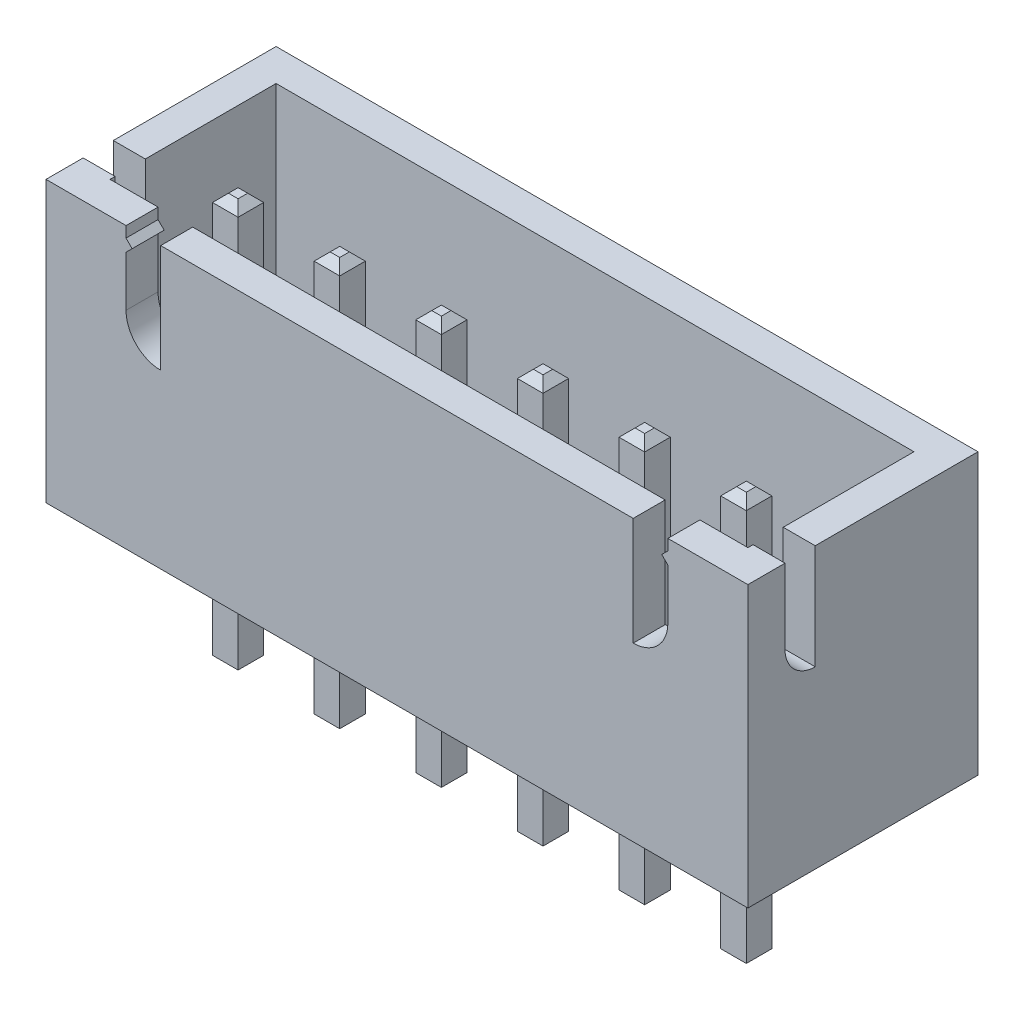
SolidWorks part; units mm, degrees
other "Camera1"
ref_plane "Front Plane" through (0, 0, 0) normal (0, 0, 1) x (1, 0, 0)
ref_plane "Top Plane" through (0, 0, 0) normal (0, 1, 0) x (1, 0, 0)
ref_plane "Right Plane" through (0, 0, 0) normal (1, 0, 0) x (0, 0, -1)
sketch "Sketch1" plane through (0, 0, 0) normal (0, 1, 0) x (1, 0, 0)
  line L1 (-8.77, 2.875) -> (8.77, 2.875)
  line L2 (-8.77, 2.875) -> (-8.77, -2.875)
  line L3 (-8.77, -2.875) -> (8.77, -2.875)
  line L4 (8.77, 2.875) -> (8.77, -2.875)
  line L5 (-8.77, 2.875) -> (8.77, -2.875) construction
  line L6 (-8.77, -2.875) -> (8.77, 2.875) construction
  point P0 (0, 0)
  dimension "D1" = 5.75
  dimension "D2" = 17.54
extrude "Boss-Extrude1" add sketch "Sketch1" along normal blind 7
shell "Shell1" thickness 0.8 removed face at (0, 7, 0)
sketch "Sketch2" plane through (8.77, 0, 0) normal (1, 0, 0) x (0, 0, -1)
  line L0 (-1.193, 7) -> (-1.193, 4.3796)
  line L1 (-2.875, 7) -> (2.875, 7) construction
  line L2 (-1.9469, 5.1335) -> (-1.9469, 7)
  line L3 (-1.9469, 7) -> (-1.193, 7)
  arc A0 (-1.193, 4.3796) -> (-1.9469, 5.1335) centre (-1.193, 5.1335) cw
extrude "Cut-Extrude1" cut sketch "Sketch2" against normal through all
sketch "Sketch3" plane through (0, 0, 2.875) normal (0, 0, 1) x (1, 0, 0)
  line L0 (-6.77, 7) -> (-6.77, 6.7289)
  line L1 (-8.77, 7) -> (8.77, 7) construction
  line L2 (-6.77, 6.7289) -> (-6.6171, 6.5761)
  line L3 (-6.6171, 6.5761) -> (-6.77, 6.4232)
  line L4 (-6.77, 6.4232) -> (-6.77, 5.1663)
  line L5 (-5.9038, 4.3001) -> (-5.9038, 7)
  line L6 (-5.9038, 7) -> (-6.77, 7)
  line L7 (-8.77, 7) -> (-8.77, 0) construction
  line L8 (0, 7) -> (0, 0) construction
  line L9 (5.9038, 7) -> (6.77, 7)
  line L10 (5.9038, 4.3001) -> (5.9038, 7)
  line L11 (6.77, 6.4232) -> (6.77, 5.1663)
  line L12 (6.6171, 6.5761) -> (6.77, 6.4232)
  line L13 (6.77, 6.7289) -> (6.6171, 6.5761)
  line L14 (6.77, 7) -> (6.77, 6.7289)
  arc A0 (-6.77, 5.1663) -> (-5.9038, 4.3001) centre (-5.9038, 5.1663) ccw
  arc A1 (6.77, 5.1663) -> (5.9038, 4.3001) centre (5.9038, 5.1663) cw
  dimension "D1" = 2
extrude "Cut-Extrude2" cut sketch "Sketch3" against normal up to next
sketch "Sketch4" plane through (0, 0, 0) normal (0, -1, 0) x (1, 0, 0)
  line L0 (-8.77, -2.875) -> (-8.77, 2.875) construction
  line L1 (-6.64, 0.845) -> (-6, 0.845)
  line L2 (-6.64, 0.845) -> (-6.64, 0.205)
  line L3 (-6.64, 0.205) -> (-6, 0.205)
  line L4 (-6, 0.845) -> (-6, 0.205)
  line L5 (-6.64, 0.845) -> (-6, 0.205) construction
  line L6 (-6.64, 0.205) -> (-6, 0.845) construction
  line L9 (-8.77, 2.875) -> (8.77, 2.875) construction
  line L10 (-4.1, 0.845) -> (-3.46, 0.845)
  line L11 (-3.46, 0.845) -> (-3.46, 0.205)
  line L12 (-4.1, 0.205) -> (-3.46, 0.205)
  line L13 (-4.1, 0.845) -> (-4.1, 0.205)
  line L14 (-1.56, 0.845) -> (-0.92, 0.845)
  line L15 (-0.92, 0.845) -> (-0.92, 0.205)
  line L16 (-1.56, 0.205) -> (-0.92, 0.205)
  line L17 (-1.56, 0.845) -> (-1.56, 0.205)
  line L18 (0.98, 0.845) -> (1.62, 0.845)
  line L19 (1.62, 0.845) -> (1.62, 0.205)
  line L20 (0.98, 0.205) -> (1.62, 0.205)
  line L21 (0.98, 0.845) -> (0.98, 0.205)
  line L22 (3.52, 0.845) -> (4.16, 0.845)
  line L23 (4.16, 0.845) -> (4.16, 0.205)
  line L24 (3.52, 0.205) -> (4.16, 0.205)
  line L25 (3.52, 0.845) -> (3.52, 0.205)
  line L26 (6.06, 0.845) -> (6.7, 0.845)
  line L27 (6.7, 0.845) -> (6.7, 0.205)
  line L28 (6.06, 0.205) -> (6.7, 0.205)
  line L29 (6.06, 0.845) -> (6.06, 0.205)
  point P0 (-6.32, 0.525)
  dimension "D1" = 0.64
  dimension "D2" = 0.64
  dimension "D3" = 2.45
  dimension "D4" = 2.35
  dimension "D5" = 6
extrude "Boss-Extrude2" add sketch "Sketch4" along normal blind 3.45 and the other way blind 6.75
chamfer "Chamfer1" distance 0.2 angle 45 48 edges at (6.06, -3.45, 0.525) (6.38, -3.45, 0.845) (6.7, -3.45, 0.525) (6.38, -3.45, 0.205) (3.52, -3.45, 0.525) (3.84, -3.45, 0.845) (4.16, -3.45, 0.525) (3.84, -3.45, 0.205) (0.98, -3.45, 0.525) (1.3, -3.45, 0.845) (1.62, -3.45, 0.525) (1.3, -3.45, 0.205) (-1.56, -3.45, 0.525) (-1.24, -3.45, 0.845) (-0.92, -3.45, 0.525) (-1.24, -3.45, 0.205) (-4.1, -3.45, 0.525) (-3.78, -3.45, 0.845) (-3.46, -3.45, 0.525) (-3.78, -3.45, 0.205) (-6.32, -3.45, 0.205) (-6.64, -3.45, 0.525) (-6.32, -3.45, 0.845) (-6, -3.45, 0.525) (6.7, 6.75, 0.525) (6.38, 6.75, 0.845) (6.06, 6.75, 0.525) (6.38, 6.75, 0.205) (4.16, 6.75, 0.525) (3.84, 6.75, 0.845) (3.52, 6.75, 0.525) (3.84, 6.75, 0.205) (1.62, 6.75, 0.525) (1.3, 6.75, 0.845) (0.98, 6.75, 0.525) (1.3, 6.75, 0.205) (-0.92, 6.75, 0.525) (-1.24, 6.75, 0.845) (-1.56, 6.75, 0.525) (-1.24, 6.75, 0.205) (-3.46, 6.75, 0.525) (-3.78, 6.75, 0.845) (-4.1, 6.75, 0.525) (-3.78, 6.75, 0.205) (-6.32, 6.75, 0.845) (-6.64, 6.75, 0.525) (-6.32, 6.75, 0.205) (-6, 6.75, 0.525)
